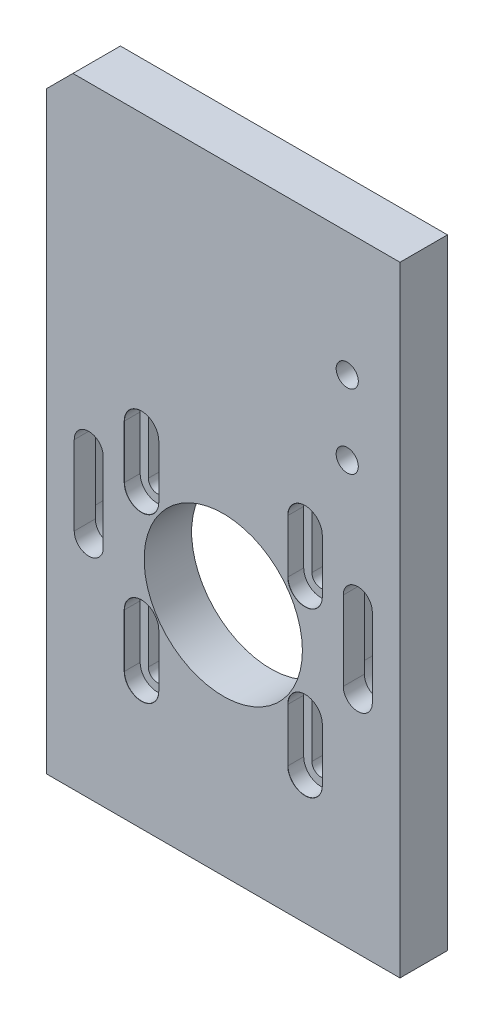
SolidWorks part; units mm, degrees
ref_plane "Front Plane" through (0, 0, 0) normal (0, 0, 1) x (1, 0, 0)
ref_plane "Top Plane" through (0, 0, 0) normal (0, 1, 0) x (1, 0, 0)
ref_plane "Right Plane" through (0, 0, 0) normal (1, 0, 0) x (0, 0, -1)
sketch "Sketch1" plane through (0, 0, 0) normal (0, 0, 1) x (1, 0, 0)
  line L0 (0, 0) -> (0, 98.1215) construction
  line L1 (-33.5, 0) -> (33.5, 0)
  line L2 (-33.5, 0) -> (-33.5, 112.5)
  line L3 (-28.5, 117.5) -> (33.5, 117.5)
  line L4 (33.5, 0) -> (33.5, 117.5)
  line L5 (-33.5, 112.5) -> (-28.5, 117.5)
  point P2 (-33.5, 117.5)
  point P7 (0, 0)
  dimension "D1" = 67
  dimension "D2" = 117.5
extrude "Boss-Extrude1" add sketch "Sketch1" along normal blind 9
sketch "Sketch2" plane through (0, 0, 9) normal (0, 0, 1) x (1, 0, 0)
  line L0 (-33.5, 0) -> (33.5, 0) construction
  line L2 (0, 0) -> (0, 83.1047) construction
  circle A0 centre (0, 44.5) radius 15
  dimension "D1" = 30
  dimension "D2" = 44.5
extrude "Motor Hole" cut sketch "Sketch2" against normal through all
hole_wizard "CBORE SLOT for M3 SHCS1" positions "Sketch9" profile "Sketch10" size "M3" standard "ANSI Metric" slot yes end condition through all
sketch "Sketch9" plane through (0, 0, 9) normal (0, 0, 1) x (1, 0, 0)
  line L0 (-15.5, 53.5) -> (-15.5, 67) construction
  line L1 (-33.5, 0) -> (33.5, 0) construction
  line L2 (-33.5, 112.5) -> (-33.5, 0) construction
  point P0 (-15.5, 60.25)
  dimension "D1" = 13.5
  dimension "D2" = 53.5
  dimension "D3" = 18
sketch "Sketch10" plane through (-15.5, 60.25, 9) normal (1, 0, 0) x (0, -1, 0)
  line L0 (0, 0) -> (0, 9)
  line L1 (0, 9) -> (1.7, 9)
  line L3 (1.7, 9) -> (1.7, 3)
  line L4 (3.25, 3) -> (1.7, 3)
  line L5 (3.25, 3) -> (3.25, 0.025)
  line L6 (3.25, 0.025) -> (3.275, 0)
  line L7 (3.275, 0) -> (0, 0)
  line L8 (-3.25, 0.025) -> (-3.275, 0) construction
  line L11 (0, -6.35) -> (0, 107.95) construction
  dimension "Thru Hole Dia." = 3.4
  dimension "Thru Hole Depth" = 9
  dimension "C'Bore Dia." = 6.5
  dimension "C'Bore Depth" = 3
  dimension "Near C'Sink Dia." = 6.55
  dimension "Near C'Sink Angle" = 90
pattern_linear "LPattern2" count 2 spacing 31 along (1, 0, 0) count 2 spacing 31 along (0, -1, 0) of "CBORE SLOT for M3 SHCS1"
hole_wizard "CBORE SLOT for M5 SHCS1" positions "Sketch13" profile "Sketch14" size "M5" standard "ANSI Metric" slot yes end condition through all
sketch "Sketch13" plane through (0, 0, 0) normal (0, 0, -1) x (-1, 0, 0)
  line L0 (-25.5, 60.25) -> (-25.5, 39.75) construction
  line L1 (-33.5, 117.5) -> (-33.5, 101.1922) construction
  line L2 (-33.5, 0) -> (-33.5, 117.5) construction
  line L4 (33.5, 0) -> (-33.5, 0) construction
  point P0 (-25.5, 50)
  dimension "D1" = 20.5
  dimension "D2" = 8
  dimension "D3" = 39.75
sketch "Sketch14" plane through (25.5, 50, 0) normal (1, 0, 0) x (0, 1, 0)
  line L0 (0, 0) -> (0, 9)
  line L1 (0, 9) -> (2.75, 9)
  line L3 (2.75, 9) -> (2.75, 5)
  line L4 (5, 5) -> (2.75, 5)
  line L5 (5, 5) -> (5, 0.025)
  line L6 (5, 0.025) -> (5.025, 0)
  line L7 (5.025, 0) -> (0, 0)
  line L8 (-5, 0.025) -> (-5.025, 0) construction
  line L11 (0, -6.35) -> (0, 107.95) construction
  dimension "Thru Hole Dia." = 5.5
  dimension "Thru Hole Depth" = 9
  dimension "C'Bore Dia." = 10
  dimension "C'Bore Depth" = 5
  dimension "Near C'Sink Dia." = 10.05
  dimension "Near C'Sink Angle" = 90
mirror "Mirror1" about plane through (0, 0, 0) normal (1, 0, 0) of "CBORE SLOT for M5 SHCS1"
hole_wizard "M5x0.8 Tapped Hole1" positions "Sketch17" profile "Sketch16" tap size "M5x0.8" standard "ANSI Metric" end condition through all
sketch "Sketch17" plane through (0, 0, 9) normal (0, 0, 1) x (1, 0, 0)
  line L0 (33.5, 117.5) -> (-28.5, 117.5) construction
  line L1 (33.5, 0) -> (33.5, 117.5) construction
  point P0 (23.5, 94)
  point P2 (23.5, 80)
  point P13 (48.4551, 93.5621)
  point P14 (0, 0)
  dimension "D1" = 14
  dimension "D2" = 23.5
  dimension "D3" = 10
cosmetic thread "Hole Thread1" parameters "D2"=5
cosmetic thread "Hole Thread2" parameters "D2"=5
sketch "Sketch16" plane through (23.5, 94, 9) normal (1, 0, 0) x (0, -1, 0)
  line L0 (0, 0) -> (0, 9)
  line L1 (0, 9) -> (2.1, 9)
  line L2 (2.1, 9) -> (2.1, 0)
  line L5 (2.1, 0) -> (0, 0)
  line L11 (0, -6.35) -> (0, 107.95) construction
  dimension "Thru Tap Drill Dia." = 4.2
  dimension "Thru Tap Drill Depth" = 9
